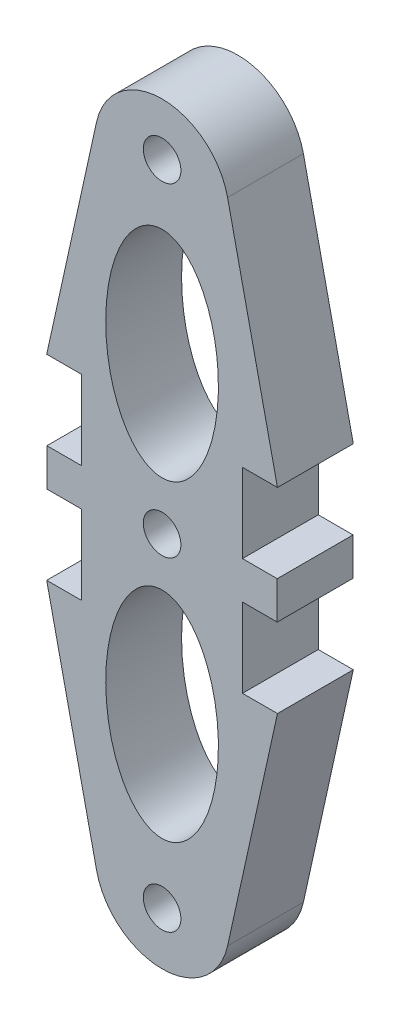
SolidWorks part; units mm, degrees
ref_plane "Front Plane" through (0, 0, 0) normal (0, 0, 1) x (1, 0, 0)
ref_plane "Top Plane" through (0, 0, 0) normal (0, 1, 0) x (1, 0, 0)
ref_plane "Right Plane" through (0, 0, 0) normal (1, 0, 0) x (0, 0, -1)
sketch "Sketch1" plane through (0, 0, 0) normal (0, 0, 1) x (1, 0, 0)
  line L0 (-213.0408, 464.8524) -> (49786.9592, 464.8524) construction
  line L1 (781.4592, 464.8524) -> (778.7761, 464.8524)
  line L2 (781.4592, 464.8524) -> (781.4592, 470.9524)
  line L3 (781.4592, 470.9524) -> (778.7592, 470.9524)
  line L4 (787.6592, -515.9255) -> (787.6592, 49484.0745) construction
  line L5 (-215.2208, 463.4024) -> (49784.7792, 463.4024) construction
  line L6 (793.8592, 470.9524) -> (793.8592, 488.4024) construction
  line L7 (-217.5077, 461.5941) -> (49782.4923, 461.5941) construction
  line L8 (786.2092, -537.0976) -> (786.2092, 49462.9024) construction
  line L9 (789.1092, -536.5976) -> (789.1092, 49463.4024) construction
  line L10 (793.8592, 464.8524) -> (796.5422, 464.8524)
  line L11 (781.4592, 470.9524) -> (793.8592, 470.9524) construction
  line L12 (793.8592, 470.9524) -> (796.5592, 470.9524)
  line L13 (793.8592, 464.8524) -> (793.8592, 470.9524)
  line L14 (778.7761, 464.8524) -> (778.7761, 461.9524)
  line L15 (796.5422, 464.8524) -> (796.5422, 461.9524)
  line L16 (786.2092, 488.4024) -> (782.6065, 488.4024) construction
  line L17 (781.4592, 461.9524) -> (778.7761, 461.9524)
  line L18 (793.8592, 470.9524) -> (793.1379, 470.9192) construction
  line L19 (781.4592, 455.8524) -> (778.7592, 455.8524)
  line L20 (781.4592, 461.9524) -> (781.4592, 455.8524)
  line L21 (793.8592, 461.9524) -> (796.5422, 461.9524)
  line L22 (793.8592, 461.9524) -> (793.8592, 455.8524)
  line L23 (793.8592, 455.8524) -> (796.5592, 455.8524)
  line L24 (778.7592, 470.9524) -> (782.6065, 488.4024)
  line L25 (792.7118, 488.4024) -> (796.5592, 470.9524)
  line L26 (792.7118, 438.4024) -> (796.5592, 455.8524)
  line L27 (789.1092, 438.4024) -> (792.7118, 438.4024) construction
  line L28 (786.2092, 438.4024) -> (782.6065, 438.4024) construction
  line L29 (778.7592, 455.8524) -> (782.6065, 438.4024)
  line L35 (789.1092, 488.4024) -> (792.7118, 488.4024) construction
  arc A0 (782.6065, 488.4024) -> (792.7118, 488.4024) centre (787.6592, 487.2884) cw
  arc A1 (782.6065, 438.4024) -> (792.7118, 438.4024) centre (787.6592, 439.5164) ccw
  circle A3 centre (787.6592, 488.4024) radius 1.45
  circle A5 centre (787.6592, 438.4024) radius 1.45
  circle A6 centre (787.6592, 463.4024) radius 1.45
  ellipse E0 centre (787.6592, 475.4481) end of major axis (787.6592, 483.7502) minor radius 4.3465
  ellipse E1 centre (787.6592, 451.3566) end of major axis (787.6592, 443.0545) minor radius 4.3465
  point P10 (786.4306, 463.4024)
  point P19 (782.4923, 461.5941)
  point P22 (780.2592, 463.4024)
  dimension "D1" = 2.9
  dimension "D3" = 6.1
  dimension "D2" = 2.7
  dimension "D4" = 25
  dimension "D5" = 12.4
extrude "Boss-Extrude1" add sketch "Sketch1" along normal blind 5.85 contours L3 A3 A5 region at (782.067, 467.9024, 0)
